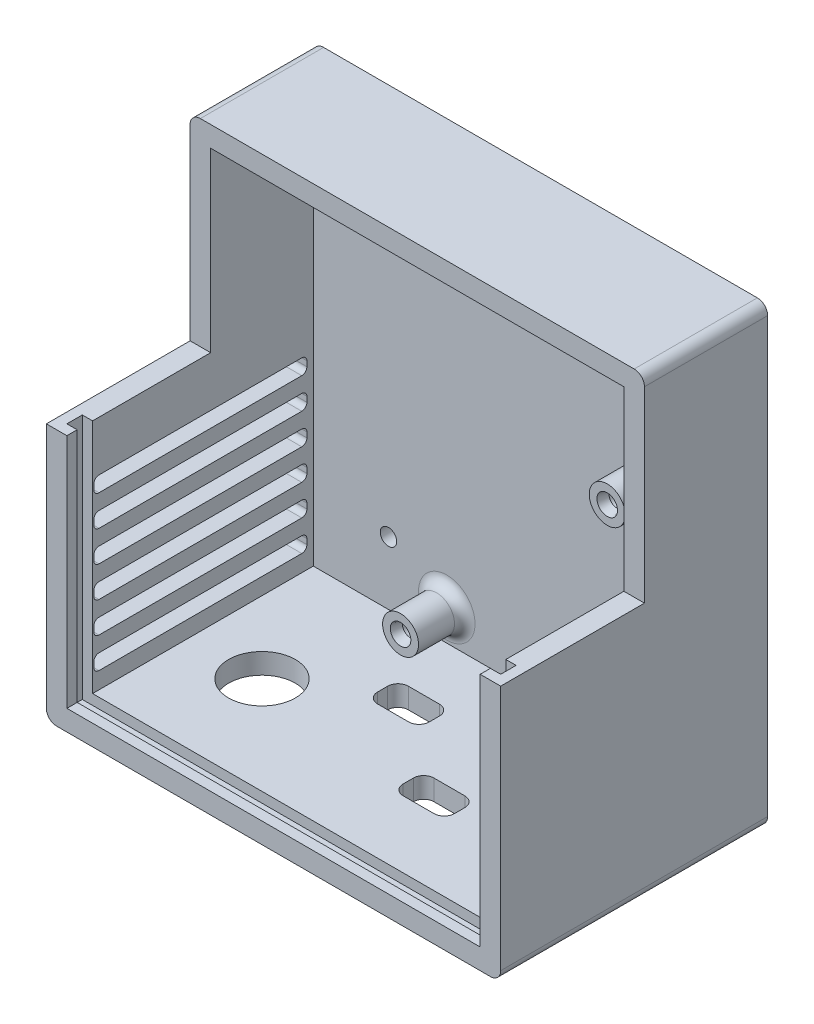
SolidWorks part; units mm, degrees
ref_plane "Front Plane" through (0, 0, 0) normal (1, 0, 0) x (0, 1, 0)
ref_plane "Top Plane" through (0, 0, 0) normal (0, 0, 1) x (0, 1, 0)
ref_plane "Right Plane" through (0, 0, 0) normal (0, 1, 0) x (-1, 0, 0)
sketch "Sketch1" plane through (0, 0, 0) normal (0, 0, 1) x (0, 1, 0)
  line L0 (-40.25, 40.25) -> (40.25, 40.25)
  line L1 (-44.25, 44.25) -> (44.25, 44.25)
  line L2 (-44.25, 44.25) -> (-44.25, -44.25)
  line L3 (-44.25, -44.25) -> (44.25, -44.25)
  line L4 (44.25, 44.25) -> (44.25, -44.25)
  line L5 (-44.25, 44.25) -> (44.25, -44.25) construction
  line L6 (-44.25, -44.25) -> (44.25, 44.25) construction
  line L7 (40.25, 40.25) -> (40.25, -40.25)
  line L8 (-40.25, -40.25) -> (40.25, -40.25)
  line L9 (-40.25, 40.25) -> (-40.25, -40.25)
  circle A0 centre (-34.25, 14.25) radius 3.5
  circle A1 centre (34.25, 14.25) radius 3.5
  circle A2 centre (7.75, -26) radius 3.5
  circle A3 centre (-34.25, 14.25) radius 1.5
  circle A4 centre (34.25, 14.25) radius 1.5
  circle A5 centre (7.75, -26) radius 1.5
  point P0 (0, 0)
  dimension "D4" = 3
  dimension "D5" = 7
  dimension "D6" = 3
  dimension "D7" = 7
  dimension "D8" = 3
  dimension "D9" = 7
  dimension "D1" = 88.5
  dimension "D2" = 88.5
  dimension "D10" = 6
  dimension "D11" = 26
  dimension "D12" = 6
  dimension "D13" = 26
  dimension "D14" = 42
  dimension "D15" = 40.25
  dimension "D3" = 4
extrude "Boss-Extrude1" add sketch "Sketch1" against normal blind 4 contours L4 L3 L2 L1
extrude "Boss-Extrude2" add sketch "Sketch1<3>" along normal blind 9 contours L4 L1 L2 L3 L9 L0 L7 L8 | A2 A5 | A1 A4 | A0 A3 region at (-42.9984, 0, 0) region at (-14.25, -37.651, 0) region at (-14.25, 30.849, 0) region at (26, 4.349, 0)
sketch "Sketch1<3>" plane through (0, 0, 0) normal (0, 0, 1) x (0, 1, 0) same geometry as "Sketch1"
chamfer "Chamfer1" distance 0.5 angle 75 3 edges at (-12.75, -34.25, 9) (27.5, 7.75, 9) (-12.75, 34.25, 9) first distance on face at (-12.75, -34.25, 9) first distance on face at (27.5, 7.75, 9) first distance on face at (-12.75, 34.25, 9)
sketch "Sketch4" plane through (0, 0, 9) normal (0, 0, 1) x (1, 0, 0)
  line L1 (-44.25, 44.25) -> (44.25, 44.25)
  line L2 (-44.25, 44.25) -> (-44.25, -44.25)
  line L3 (-44.25, -44.25) -> (44.25, -44.25)
  line L4 (44.25, 44.25) -> (44.25, -44.25)
  line L5 (-40.25, -40.25) -> (40.25, -40.25)
  line L6 (-40.25, -40.25) -> (-40.25, 40.25)
  line L7 (-40.25, 40.25) -> (40.25, 40.25)
  line L8 (40.25, -40.25) -> (40.25, 40.25)
extrude "Boss-Extrude3" add sketch "Sketch4" along normal blind 39
sketch "Sketch5" plane through (0, -44.25, 0) normal (0, -1, 0) x (1, 0, 0)
  line L0 (-44.25, -4) -> (-44.25, 48) construction
  line L1 (7.25, 30) -> (13.25, 30)
  line L2 (5.25, 28) -> (5.25, 26)
  line L3 (7.25, 24) -> (13.25, 24)
  line L4 (15.25, 28) -> (15.25, 26)
  line L5 (5.25, 30) -> (15.25, 24) construction
  line L6 (5.25, 24) -> (15.25, 30) construction
  line L7 (-44.25, -4) -> (44.25, -4) construction
  line L8 (-10.75, 17) -> (-4.67, 17)
  line L9 (-12.75, 15) -> (-12.75, 13)
  line L10 (-10.75, 11) -> (-4.67, 11)
  line L11 (-2.67, 15) -> (-2.67, 13)
  line L12 (-12.75, 17) -> (-2.67, 11) construction
  line L13 (-12.75, 11) -> (-2.67, 17) construction
  arc A0 (7.25, 30) -> (5.25, 28) centre (7.25, 28) ccw
  arc A1 (15.25, 28) -> (13.25, 30) centre (13.25, 28) ccw
  arc A2 (15.25, 26) -> (13.25, 24) centre (13.25, 26) cw
  arc A3 (5.25, 26) -> (7.25, 24) centre (7.25, 26) ccw
  arc A4 (-10.75, 17) -> (-12.75, 15) centre (-10.75, 15) ccw
  arc A5 (-4.67, 17) -> (-2.67, 15) centre (-4.67, 15) cw
  arc A6 (-2.67, 13) -> (-4.67, 11) centre (-4.67, 13) cw
  arc A7 (-12.75, 13) -> (-10.75, 11) centre (-10.75, 13) ccw
  circle A8 centre (-26.25, 24) radius 6.5
  point P0 (10.25, 27)
  point P7 (-7.71, 14)
  dimension "D9" = 2
  dimension "D10" = 2
  dimension "D11" = 2
  dimension "D12" = 2
  dimension "D13" = 2
  dimension "D14" = 2
  dimension "D15" = 2
  dimension "D16" = 2
  dimension "D18" = 13
  dimension "D1" = 49.5
  dimension "D2" = 31.5
  dimension "D3" = 10.08
  dimension "D4" = 15
  dimension "D5" = 6
  dimension "D6" = 28
  dimension "D7" = 6
  dimension "D8" = 10
  dimension "D17" = 13.5
extrude "Cut-Extrude1" cut sketch "Sketch5" against normal blind 16
fillet "Fillet1" radius 2 1 edges at (44.25, -44.25, 22)
fillet "Fillet2" radius 2 1 edges at (-44.25, -44.25, 22)
fillet "Fillet3" radius 2 1 edges at (44.25, 44.25, 22)
fillet "Fillet4" radius 2 1 edges at (-44.25, 44.25, 22)
fillet "Fillet5" radius 2 1 edges at (22.5, 7.75, 0)
fillet "Fillet6" radius 2 1 edges at (-17.75, -34.25, 0)
fillet "Fillet7" radius 2 1 edges at (-17.75, 34.25, 0)
sketch "Sketch6" plane through (-44.25, 0, 0) normal (-1, 0, 0) x (0, -1, 0)
  line L0 (-42.25, 22) -> (42.25, 22) construction
  line L1 (36, 1.25) -> (35, 1.25)
  line L2 (37, 2.25) -> (37, 41.75)
  line L3 (36, 42.75) -> (35, 42.75)
  line L4 (34, 2.25) -> (34, 41.75)
  line L5 (37, 1.25) -> (34, 42.75) construction
  line L6 (37, 42.75) -> (34, 1.25) construction
  line L7 (-42.25, 48) -> (-42.25, -4) construction
  line L8 (42.25, -4) -> (42.25, 48) construction
  line L10 (42.25, -4) -> (-42.25, -4) construction
  line L56 (31, 2.25) -> (31, 41.75)
  line L57 (30, 1.25) -> (29, 1.25)
  line L58 (28, 2.25) -> (28, 41.75)
  line L59 (30, 42.75) -> (29, 42.75)
  line L60 (25, 2.25) -> (25, 41.75)
  line L61 (24, 1.25) -> (23, 1.25)
  line L62 (22, 2.25) -> (22, 41.75)
  line L63 (24, 42.75) -> (23, 42.75)
  line L64 (19, 2.25) -> (19, 41.75)
  line L65 (18, 1.25) -> (17, 1.25)
  line L66 (16, 2.25) -> (16, 41.75)
  line L67 (18, 42.75) -> (17, 42.75)
  line L68 (13, 2.25) -> (13, 41.75)
  line L69 (12, 1.25) -> (11, 1.25)
  line L70 (10, 2.25) -> (10, 41.75)
  line L71 (12, 42.75) -> (11, 42.75)
  line L72 (7, 2.25) -> (7, 41.75)
  line L73 (6, 1.25) -> (5, 1.25)
  line L74 (4, 2.25) -> (4, 41.75)
  line L75 (6, 42.75) -> (5, 42.75)
  line L100 (1, 2.25) -> (1, 41.75) [skipped]
  line L101 (0, 1.25) -> (-1, 1.25) [skipped]
  line L102 (-2, 2.25) -> (-2, 41.75) [skipped]
  line L103 (0, 42.75) -> (-1, 42.75) [skipped]
  line L104 (-5, 2.25) -> (-5, 41.75) [skipped]
  line L105 (-6, 1.25) -> (-7, 1.25) [skipped]
  line L106 (-8, 2.25) -> (-8, 41.75) [skipped]
  line L107 (-6, 42.75) -> (-7, 42.75) [skipped]
  line L108 (-11, 2.25) -> (-11, 41.75) [skipped]
  line L109 (-12, 1.25) -> (-13, 1.25) [skipped]
  line L110 (-14, 2.25) -> (-14, 41.75) [skipped]
  line L111 (-12, 42.75) -> (-13, 42.75) [skipped]
  line L112 (-17, 2.25) -> (-17, 41.75) [skipped]
  line L113 (-18, 1.25) -> (-19, 1.25) [skipped]
  line L114 (-20, 2.25) -> (-20, 41.75) [skipped]
  line L115 (-18, 42.75) -> (-19, 42.75) [skipped]
  line L116 (-23, 2.25) -> (-23, 41.75) [skipped]
  line L117 (-24, 1.25) -> (-25, 1.25) [skipped]
  line L118 (-26, 2.25) -> (-26, 41.75) [skipped]
  line L119 (-24, 42.75) -> (-25, 42.75) [skipped]
  line L120 (-29, 2.25) -> (-29, 41.75) [skipped]
  line L121 (-30, 1.25) -> (-31, 1.25) [skipped]
  line L122 (-30, 42.75) -> (-31, 42.75) [skipped]
  line L123 (-32, 2.25) -> (-32, 41.75) [skipped]
  arc A0 (37, 41.75) -> (36, 42.75) centre (36, 41.75) ccw
  arc A1 (35, 42.75) -> (34, 41.75) centre (35, 41.75) ccw
  arc A2 (37, 2.25) -> (36, 1.25) centre (36, 2.25) cw
  arc A3 (34, 2.25) -> (35, 1.25) centre (35, 2.25) ccw
  arc A4 (31, 2.25) -> (30, 1.25) centre (30, 2.25) cw
  arc A5 (31, 41.75) -> (30, 42.75) centre (30, 41.75) ccw
  arc A6 (28, 2.25) -> (29, 1.25) centre (29, 2.25) ccw
  arc A7 (29, 42.75) -> (28, 41.75) centre (29, 41.75) ccw
  arc A8 (25, 2.25) -> (24, 1.25) centre (24, 2.25) cw
  arc A9 (25, 41.75) -> (24, 42.75) centre (24, 41.75) ccw
  arc A10 (22, 2.25) -> (23, 1.25) centre (23, 2.25) ccw
  arc A11 (23, 42.75) -> (22, 41.75) centre (23, 41.75) ccw
  arc A12 (19, 2.25) -> (18, 1.25) centre (18, 2.25) cw
  arc A13 (19, 41.75) -> (18, 42.75) centre (18, 41.75) ccw
  arc A14 (16, 2.25) -> (17, 1.25) centre (17, 2.25) ccw
  arc A15 (17, 42.75) -> (16, 41.75) centre (17, 41.75) ccw
  arc A16 (13, 2.25) -> (12, 1.25) centre (12, 2.25) cw
  arc A17 (13, 41.75) -> (12, 42.75) centre (12, 41.75) ccw
  arc A18 (10, 2.25) -> (11, 1.25) centre (11, 2.25) ccw
  arc A19 (11, 42.75) -> (10, 41.75) centre (11, 41.75) ccw
  arc A20 (7, 2.25) -> (6, 1.25) centre (6, 2.25) cw
  arc A21 (7, 41.75) -> (6, 42.75) centre (6, 41.75) ccw
  arc A22 (4, 2.25) -> (5, 1.25) centre (5, 2.25) ccw
  arc A23 (5, 42.75) -> (4, 41.75) centre (5, 41.75) ccw
  arc A48 (1, 2.25) -> (0, 1.25) centre (0, 2.25) cw [skipped]
  arc A49 (1, 41.75) -> (0, 42.75) centre (0, 41.75) ccw [skipped]
  arc A50 (-2, 2.25) -> (-1, 1.25) centre (-1, 2.25) ccw [skipped]
  arc A51 (-1, 42.75) -> (-2, 41.75) centre (-1, 41.75) ccw [skipped]
  arc A52 (-5, 2.25) -> (-6, 1.25) centre (-6, 2.25) cw [skipped]
  arc A53 (-5, 41.75) -> (-6, 42.75) centre (-6, 41.75) ccw [skipped]
  arc A54 (-8, 2.25) -> (-7, 1.25) centre (-7, 2.25) ccw [skipped]
  arc A55 (-7, 42.75) -> (-8, 41.75) centre (-7, 41.75) ccw [skipped]
  arc A56 (-11, 2.25) -> (-12, 1.25) centre (-12, 2.25) cw [skipped]
  arc A57 (-11, 41.75) -> (-12, 42.75) centre (-12, 41.75) ccw [skipped]
  arc A58 (-14, 2.25) -> (-13, 1.25) centre (-13, 2.25) ccw [skipped]
  arc A59 (-13, 42.75) -> (-14, 41.75) centre (-13, 41.75) ccw [skipped]
  arc A60 (-17, 2.25) -> (-18, 1.25) centre (-18, 2.25) cw [skipped]
  arc A61 (-17, 41.75) -> (-18, 42.75) centre (-18, 41.75) ccw [skipped]
  arc A62 (-20, 2.25) -> (-19, 1.25) centre (-19, 2.25) ccw [skipped]
  arc A63 (-19, 42.75) -> (-20, 41.75) centre (-19, 41.75) ccw [skipped]
  arc A64 (-23, 2.25) -> (-24, 1.25) centre (-24, 2.25) cw [skipped]
  arc A65 (-23, 41.75) -> (-24, 42.75) centre (-24, 41.75) ccw [skipped]
  arc A66 (-26, 2.25) -> (-25, 1.25) centre (-25, 2.25) ccw [skipped]
  arc A67 (-25, 42.75) -> (-26, 41.75) centre (-25, 41.75) ccw [skipped]
  arc A68 (-29, 2.25) -> (-30, 1.25) centre (-30, 2.25) cw [skipped]
  arc A69 (-29, 41.75) -> (-30, 42.75) centre (-30, 41.75) ccw [skipped]
  arc A70 (-31, 42.75) -> (-32, 41.75) centre (-31, 41.75) ccw [skipped]
  arc A71 (-32, 2.25) -> (-31, 1.25) centre (-31, 2.25) ccw [skipped]
  point P0 (35.5, 22)
  dimension "D5" = 1
  dimension "D6" = 1
  dimension "D7" = 1
  dimension "D8" = 1
  dimension "D1" = 5.25
  dimension "D2" = 3
  dimension "D3" = 5.25
  dimension "D4" = 12
extrude "Cut-Extrude2" cut sketch "Sketch6" against normal blind 10
ref_plane "Plane1" through (-54.25, 0, 0) normal (-1, 0, 0) x (0, 0, 1)
sketch "Sketch9" plane through (-44.25, 0, 0) normal (-1, 0, 0) x (0, 0, 1)
  line L0 (48, 42.25) -> (48, -42.25) construction
  line L5 (48, 44.25) -> (20, 44.25)
  line L6 (48, 44.25) -> (48, 5.75)
  line L7 (48, 5.75) -> (20, 5.75)
  line L8 (48, -44.25) -> (-4, -44.25) construction
  line L9 (20, 44.25) -> (20, 5.75)
  line L10 (48, 44.25) -> (20, 5.75) construction
  line L12 (48, 5.75) -> (20, 44.25) construction
  line L13 (-4, 44.25) -> (48, 44.25) construction
  line L14 (-4, -42.25) -> (-4, 42.25) construction
  point P0 (34, 25)
  dimension "D1" = 50
  dimension "D2" = 24
extrude "Cut-Extrude3" cut sketch "Sketch9" against normal blind 88.5
sketch "Sketch13" plane through (0, 0, -4) normal (0, 0, -1) x (1, 0, 0)
  line L0 (-25.61, 28) -> (10.19, -28) construction
  line L1 (-25.61, -28) -> (10.19, 28) construction
  line L3 (-44.25, 42.25) -> (-44.25, -42.25) construction
  circle A4 centre (-25.61, 28) radius 1.6
  circle A5 centre (10.19, 28) radius 1.6
  circle A6 centre (-25.61, -28) radius 1.6
  circle A7 centre (10.19, -28) radius 1.6
  point P8 (-7.71, 0)
  dimension "D1" = 3.2
  dimension "D2" = 3.2
  dimension "D3" = 3.2
  dimension "D4" = 3.2
  dimension "D5" = 35.8
  dimension "D6" = 56
  dimension "D7" = 36.54
extrude "Cut-Extrude5" cut sketch "Sketch13" against normal blind 10
sketch "Sketch14" plane through (0, 5.75, 0) normal (0, 1, 0) x (-1, 0, 0)
  line L0 (-40.25, 20) -> (-40.25, 48) construction
  line L1 (-40.25, 46) -> (-42.25, 46)
  line L2 (-40.25, 46) -> (-40.25, 43)
  line L3 (-40.25, 43) -> (-42.25, 43)
  line L4 (-42.25, 46) -> (-42.25, 43)
  line L5 (-44.25, 48) -> (-40.25, 48) construction
  line L6 (-44.25, 20) -> (-44.25, 48) construction
  dimension "D1" = 2
  dimension "D2" = 2
  dimension "D3" = 3
extrude "Cut-Extrude6" cut sketch "Sketch14" against normal blind 48
sketch "Sketch15" plane through (0, 5.75, 0) normal (0, 1, 0) x (-1, 0, 0)
  line L0 (40.25, 20) -> (40.25, 48) construction
  line L1 (40.25, 46) -> (42.25, 46)
  line L2 (40.25, 46) -> (40.25, 43)
  line L3 (40.25, 43) -> (42.25, 43)
  line L4 (42.25, 46) -> (42.25, 43)
  line L5 (40.25, 48) -> (44.25, 48) construction
  dimension "D1" = 2
  dimension "D2" = 2
  dimension "D3" = 3
extrude "Cut-Extrude7" cut sketch "Sketch15" against normal blind 48
sketch "Sketch16" plane through (0, -40.25, 0) normal (0, 1, 0) x (-1, 0, 0)
  line L1 (-40.25, 46) -> (40.25, 46)
  line L2 (-40.25, 46) -> (-40.25, 43)
  line L3 (-40.25, 43) -> (40.25, 43)
  line L4 (40.25, 46) -> (40.25, 43)
extrude "Cut-Extrude8" cut sketch "Sketch16" against normal blind 2
